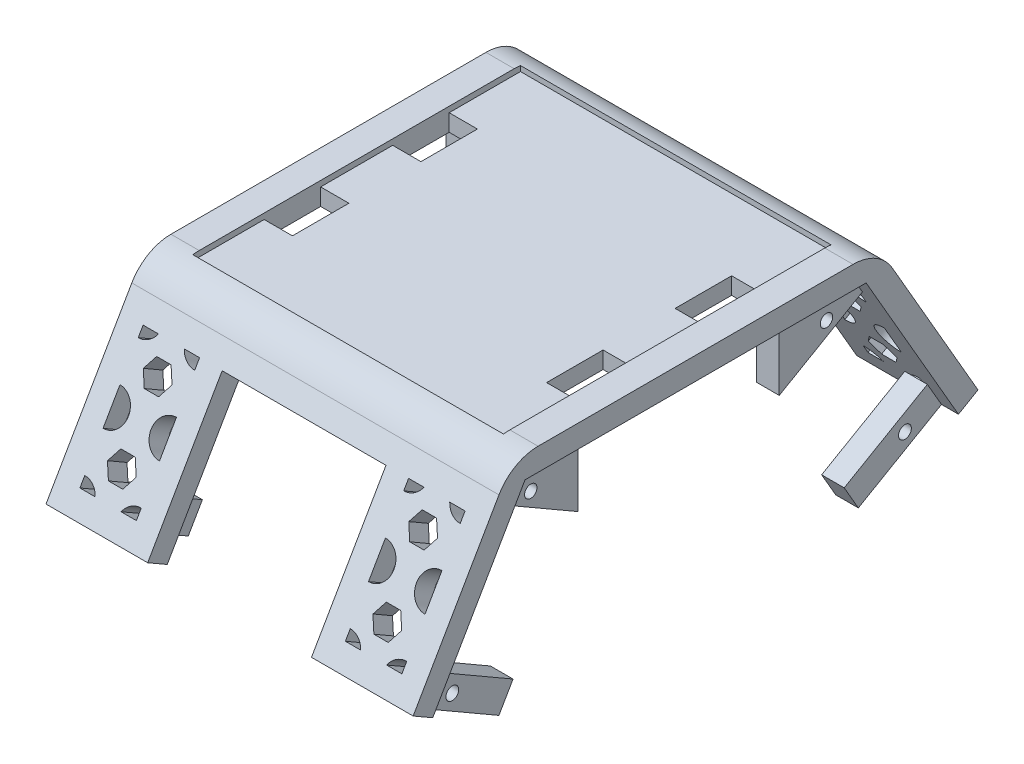
SolidWorks part; units mm, degrees
ref_plane "Front Plane" through (0, 0, 0) normal (0, 0, 1) x (1, 0, 0)
ref_plane "Top Plane" through (0, 0, 0) normal (0, 1, 0) x (1, 0, 0)
ref_plane "Right Plane" through (0, 0, 0) normal (1, 0, 0) x (0, 0, -1)
sketch "Sketch1" plane through (0, 0, 0) normal (0, 1, 0) x (1, 0, 0)
  line L0 (0, 298.9056) -> (0, -308.5053) construction
  line L1 (370.8017, 0) -> (-385.0846, 0) construction
  line L3 (-32.5, 32.5) -> (32.5, 32.5)
  line L4 (-32.5, 32.5) -> (-32.5, -32.5)
  line L5 (-32.5, -32.5) -> (32.5, -32.5)
  line L6 (32.5, 32.5) -> (32.5, -32.5)
  line L7 (-32.5, 32.5) -> (32.5, -32.5) construction
  line L8 (-32.5, -32.5) -> (32.5, 32.5) construction
  point P1 (0, 0)
  dimension "D1" = 65
  dimension "D2" = 65
extrude "Boss-Extrude1" add sketch "Sketch1" along normal blind 4
sketch "Sketch2" plane through (0, 4, 0) normal (0, 1, 0) x (1, 0, 0)
  line L1 (-27.5, 29) -> (27.5, 29)
  line L2 (-27.5, 29) -> (-27.5, -29)
  line L3 (-27.5, -29) -> (27.5, -29)
  line L4 (27.5, 29) -> (27.5, -29)
  line L5 (-27.5, 29) -> (27.5, -29) construction
  line L6 (-27.5, -29) -> (27.5, 29) construction
  point P1 (0, 0)
  dimension "D1" = 58
  dimension "D2" = 55
extrude "Cut-Extrude1" cut sketch "Sketch2" against normal blind 1 contours L2 L3 L4 L1
sketch "Sketch3" plane through (0, 0, 0) normal (1, 0, 0) x (0, 0, -1)
  line L0 (-32.5, 4) -> (-50, -26.3109)
  line L1 (-50, -26.3109) -> (-46.5359, -28.3109)
  line L2 (-46.5359, -28.3109) -> (-29.0359, 2)
  line L4 (-32.5, 4) -> (-29.0359, 2)
  line L5 (-32.5, 4) -> (32.5, 4) construction
  line L6 (0, 0) -> (0, -39.2948) construction
  line L7 (-32.5, 0) -> (32.5, 0) construction
  line L8 (32.5, 4) -> (50, -26.3109)
  line L9 (50, -26.3109) -> (46.5359, -28.3109)
  line L10 (46.5359, -28.3109) -> (29.0359, 2)
  line L11 (32.5, 4) -> (29.0359, 2)
  dimension "D1" = 120
  dimension "D2" = 4
  dimension "D3" = 35
extrude "Boss-Extrude2" add sketch "Sketch3" against normal up to surface (32.5 mm away) and the other way through all up to face at (-32.5, 2, 0)
fillet "Fillet1" radius 8 2 edges at (0, 4, -32.5) (0, 4, 32.5)
sketch "Sketch4" plane through (0, 15.0729, 26.1071) normal (0, 0.5, 0.866) x (1, 0, 0)
  line L0 (-32.5, -47.7859) -> (-32.5, -17.4047) construction
  line L1 (-14.5, -21.4047) -> (14.5, -21.4047)
  line L2 (-14.5, -21.4047) -> (-14.5, -60.4588)
  line L3 (-14.5, -60.4588) -> (14.5, -60.4588)
  line L4 (14.5, -21.4047) -> (14.5, -60.4588)
  line L5 (32.5, -17.4047) -> (-32.5, -17.4047) construction
  line L6 (-32.5, -47.7859) -> (32.5, -47.7859) construction
  line L7 (-28.5, -21.4047) -> (-25.7844, -21.4047)
  line L8 (-28.5, -21.4047) -> (-28.5, -23.1298)
  line L9 (-28.5, -43.7859) -> (-25.7844, -43.7859)
  line L10 (-18.5, -21.4047) -> (-18.5, -23.1298)
  line L11 (-28.5, -32.5953) -> (-18.5, -32.5953) construction
  line L12 (-23.5, -46.7859) -> (-23.5, -21.4047) construction
  line L13 (-28.5, -29.5953) -> (-28.5, -35.5953)
  line L14 (-28.5, -42.0608) -> (-28.5, -43.7859)
  line L15 (-21.2156, -43.7859) -> (-18.5, -43.7859)
  line L16 (-18.5, -42.0608) -> (-18.5, -43.7859)
  line L17 (-18.5, -29.5953) -> (-18.5, -35.5953)
  line L18 (-21.2156, -21.4047) -> (-18.5, -21.4047)
  line L19 (-35.4814, -26.2503) -> (-16.7068, -26.2503) construction
  line L20 (-20.9544, -26.2503) -> (-22.2272, -24.0457)
  line L21 (-22.2272, -24.0457) -> (-24.7728, -24.0457)
  line L22 (-24.7728, -24.0457) -> (-26.0456, -26.2503)
  line L23 (-26.0456, -26.2503) -> (-24.7728, -28.4549)
  line L24 (-24.7728, -28.4549) -> (-22.2272, -28.4549)
  line L25 (-22.2272, -28.4549) -> (-20.9544, -26.2503)
  line L26 (-22.2272, -36.7357) -> (-20.9544, -38.9403)
  line L27 (-24.7728, -36.7357) -> (-22.2272, -36.7357)
  line L28 (-26.0456, -38.9403) -> (-24.7728, -36.7357)
  line L29 (-24.7728, -41.1449) -> (-26.0456, -38.9403)
  line L30 (-22.2272, -41.1449) -> (-24.7728, -41.1449)
  line L31 (-20.9544, -38.9403) -> (-22.2272, -41.1449)
  line L32 (0, -23.8749) -> (0, 23.8749) construction
  line L33 (35.4814, -26.2503) -> (16.7068, -26.2503) construction
  line L34 (23.5, -46.7859) -> (23.5, -21.4047) construction
  line L35 (28.5, -32.5953) -> (18.5, -32.5953) construction
  line L36 (20.9544, -38.9403) -> (22.2272, -41.1449)
  line L37 (22.2272, -41.1449) -> (24.7728, -41.1449)
  line L38 (24.7728, -41.1449) -> (26.0456, -38.9403)
  line L39 (26.0456, -38.9403) -> (24.7728, -36.7357)
  line L40 (24.7728, -36.7357) -> (22.2272, -36.7357)
  line L41 (22.2272, -36.7357) -> (20.9544, -38.9403)
  line L42 (22.2272, -28.4549) -> (20.9544, -26.2503)
  line L43 (24.7728, -28.4549) -> (22.2272, -28.4549)
  line L44 (26.0456, -26.2503) -> (24.7728, -28.4549)
  line L45 (24.7728, -24.0457) -> (26.0456, -26.2503)
  line L46 (22.2272, -24.0457) -> (24.7728, -24.0457)
  line L47 (20.9544, -26.2503) -> (22.2272, -24.0457)
  line L48 (21.2156, -21.4047) -> (18.5, -21.4047)
  line L49 (18.5, -29.5953) -> (18.5, -35.5953)
  line L50 (18.5, -42.0608) -> (18.5, -43.7859)
  line L51 (21.2156, -43.7859) -> (18.5, -43.7859)
  line L52 (28.5, -42.0608) -> (28.5, -43.7859)
  line L53 (28.5, -29.5953) -> (28.5, -35.5953)
  line L54 (18.5, -21.4047) -> (18.5, -23.1298)
  line L55 (28.5, -43.7859) -> (25.7844, -43.7859)
  line L56 (28.5, -21.4047) -> (28.5, -23.1298)
  line L57 (28.5, -21.4047) -> (25.7844, -21.4047)
  arc A0 (-28.5, -23.1298) -> (-25.7844, -21.4047) centre (-28.5, -20.1298) ccw
  arc A1 (-28.5, -29.5953) -> (-28.5, -35.5953) centre (-28.5, -32.5953) cw
  arc A2 (-28.5, -42.0608) -> (-25.7844, -43.7859) centre (-28.5, -45.0608) cw
  arc A3 (-18.5, -42.0608) -> (-21.2156, -43.7859) centre (-18.5, -45.0608) ccw
  arc A4 (-18.5, -29.5953) -> (-18.5, -35.5953) centre (-18.5, -32.5953) ccw
  arc A5 (-18.5, -23.1298) -> (-21.2156, -21.4047) centre (-18.5, -20.1298) cw
  circle A6 centre (-23.5, -26.2503) radius 2.2046 construction
  circle A7 centre (23.5, -26.2503) radius 2.2046 construction
  arc A8 (18.5, -23.1298) -> (21.2156, -21.4047) centre (18.5, -20.1298) ccw
  arc A9 (18.5, -29.5953) -> (18.5, -35.5953) centre (18.5, -32.5953) cw
  arc A10 (18.5, -42.0608) -> (21.2156, -43.7859) centre (18.5, -45.0608) cw
  arc A11 (28.5, -42.0608) -> (25.7844, -43.7859) centre (28.5, -45.0608) ccw
  arc A12 (28.5, -29.5953) -> (28.5, -35.5953) centre (28.5, -32.5953) ccw
  arc A13 (28.5, -23.1298) -> (25.7844, -21.4047) centre (28.5, -20.1298) cw
  point P4 (0, -21.4047)
  point P46 (0, 0)
  dimension "D7" = 3
  dimension "D1" = 18
  dimension "D2" = 4
  dimension "D3" = 4
  dimension "D4" = 4
  dimension "D5" = 4
  dimension "D6" = 4
  dimension "D8" = 6.345
extrude "Cut-Extrude2" cut sketch "Sketch4" against normal through all both and the other way through all
mirror "Mirror1" about plane through (0, 0, 0) normal (0, 0, 1) of "Cut-Extrude2"
sketch "Sketch5" plane through (32.5, 0, 0) normal (1, 0, 0) x (0, 0, -1)
  line L0 (-30.1906, 0) -> (30.1906, 0) construction
  line L1 (-17.8135, 0) -> (-30.1906, 0)
  line L2 (-17.8135, 0) -> (-17.8135, -12.5622)
  line L3 (-17.8135, -12.5622) -> (-32.5359, -4.0622)
  line L5 (-46.5359, -28.3109) -> (-30.1906, 0) construction
  line L6 (-32.5359, -4.0622) -> (-30.1906, 0)
  line L7 (0, 23.8749) -> (0, -23.8749) construction
  line L8 (17.8135, -12.5622) -> (32.5359, -4.0622)
  line L9 (17.8135, 0) -> (17.8135, -12.5622)
  line L10 (17.8135, 0) -> (30.1906, 0)
  line L11 (32.5359, -4.0622) -> (30.1906, 0)
  line L12 (-46.5359, -28.3109) -> (-44.0359, -23.9808)
  line L13 (-46.5359, -28.3109) -> (-31.8135, -36.8109)
  line L14 (-44.0359, -23.9808) -> (-29.3135, -32.4808)
  line L15 (-31.8135, -36.8109) -> (-29.3135, -32.4808)
  line L16 (-29.3135, -32.4808) -> (-17.8135, -12.5622) construction
  line L17 (44.0359, -23.9808) -> (29.3135, -32.4808)
  line L18 (31.8135, -36.8109) -> (29.3135, -32.4808)
  line L19 (46.5359, -28.3109) -> (31.8135, -36.8109)
  line L20 (46.5359, -28.3109) -> (44.0359, -23.9808)
  point P2 (-39.7728, -46.0418)
  point P26 (-19.3135, -15.1603)
  dimension "D1" = 23
  dimension "D2" = 17
  dimension "D3" = 5
extrude "Boss-Extrude3" add sketch "Sketch5" against normal blind 4 from offset 3 offset against normal yes
mirror "Mirror2" about plane through (0, 0, 0) normal (1, 0, 0) of "Boss-Extrude3"
sketch "Sketch6" plane through (0, 3, 0) normal (0, 1, 0) x (1, 0, 0)
  line L0 (-27.5, 29) -> (-27.5, -29) construction
  line L1 (-27.5, 16.3753) -> (-22.5, 16.3753)
  line L2 (-27.5, 16.3753) -> (-27.5, 6.3753)
  line L3 (-27.5, 6.3753) -> (-22.5, 6.3753)
  line L4 (-22.5, 16.3753) -> (-22.5, 6.3753)
  line L5 (0, -22.446) -> (0, 22.446) construction
  line L6 (27.5, 6.3753) -> (22.5, 6.3753)
  line L7 (22.5, 16.3753) -> (22.5, 6.3753)
  line L8 (27.5, 16.3753) -> (22.5, 16.3753)
  line L9 (27.5, 16.3753) -> (27.5, 6.3753)
  line L10 (-22.446, 0) -> (22.446, 0) construction
  line L11 (27.5, -16.3753) -> (27.5, -6.3753)
  line L12 (27.5, -16.3753) -> (22.5, -16.3753)
  line L13 (22.5, -16.3753) -> (22.5, -6.3753)
  line L14 (27.5, -6.3753) -> (22.5, -6.3753)
  line L15 (-27.5, -6.3753) -> (-22.5, -6.3753)
  line L16 (-22.5, -16.3753) -> (-22.5, -6.3753)
  line L17 (-27.5, -16.3753) -> (-22.5, -16.3753)
  line L18 (-27.5, -16.3753) -> (-27.5, -6.3753)
  dimension "D1" = 10
  dimension "D2" = 5
extrude "Cut-Extrude3" cut sketch "Sketch6" against normal through all both and the other way through all
sketch "Sketch7" plane through (29.5, 0, 0) normal (1, 0, 0) x (0, 0, -1)
  circle A0 centre (-40.0684, -29.2906) radius 1.1365
  circle A1 centre (-26.1781, -5.2502) radius 1.1
extrude "Cut-Extrude4" cut sketch "Sketch7" against normal through all both and the other way through all
mirror "Mirror3" about plane through (0, 0, 0) normal (0, 0, 1) of "Cut-Extrude4"
